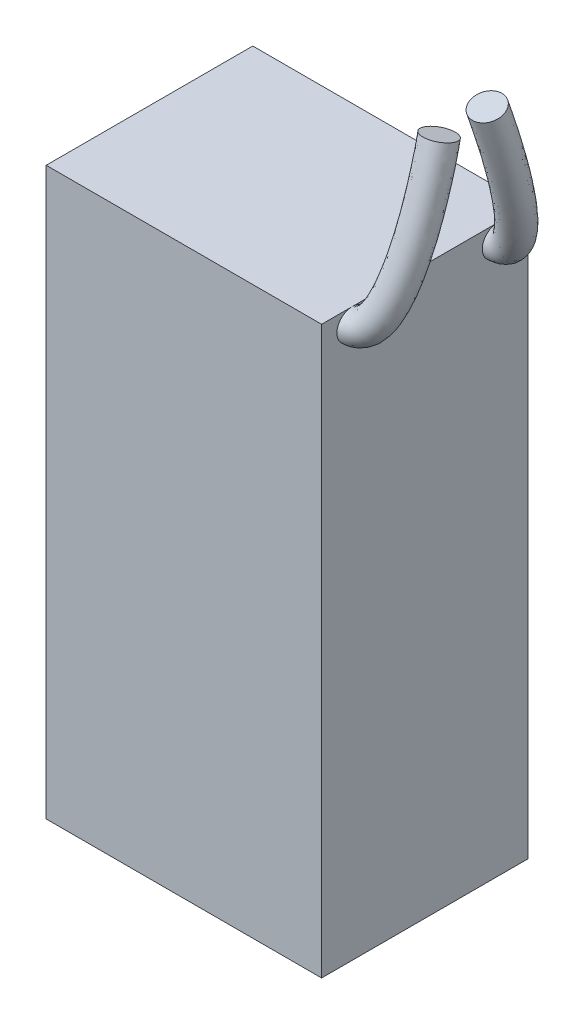
SolidWorks part; units mm, degrees
ref_plane "Спереди" through (0, 0, 0) normal (0, 0, 1) x (1, 0, 0)
ref_plane "Сверху" through (0, 0, 0) normal (0, 1, 0) x (1, 0, 0)
ref_plane "Справа" through (0, 0, 0) normal (1, 0, 0) x (0, 0, -1)
sketch "Эскиз1" plane through (0, 0, 0) normal (0, 1, 0) x (1, 0, 0)
  line L1 (-18, 13.5) -> (18, 13.5)
  line L2 (-18, 13.5) -> (-18, -13.5)
  line L3 (-18, -13.5) -> (18, -13.5)
  line L4 (18, 13.5) -> (18, -13.5)
  line L5 (-18, 13.5) -> (18, -13.5) construction
  line L6 (-18, -13.5) -> (18, 13.5) construction
  point P0 (0, 0)
  dimension "D1" = 36
  dimension "D2" = 27
extrude "Бобышка-Вытянуть1" add sketch "Эскиз1" along normal blind 74
sketch "Эскиз2" plane through (18, 0, 0) normal (1, 0, 0) x (0, 0, -1)
  line L0 (-13.5, 74) -> (13.5, 74) construction
  line L3 (-13.5, 74) -> (-13.5, 0) construction
  circle A0 centre (-9.5, 72) radius 2
  dimension "D1" = 4
  dimension "D2" = 4
sketch "Эскиз7" plane through (18, 0, 0) normal (1, 0, 0) x (0, 0, -1)
  line L0 (13.5, 74) -> (13.5, 0) construction
  line L1 (-13.5, 74) -> (13.5, 74) construction
  circle A0 centre (9.5, 72) radius 2
  dimension "D1" = 4
  dimension "D2" = 4
ref_axis "Ось1" through (18, 72, 9.5) along (-1, 0, 0)
ref_plane "Плоскость1" through (0, 8.8108, 28.8189) normal (0, 0.2924, 0.9563) x (-1, 0, 0)
ref_axis "Ось2" through (18, 72, -9.5) along (-1, 0, 0)
ref_plane "Плоскость2" through (0, 8.8108, -28.8189) normal (0, 0.2924, -0.9563) x (-1, 0, 0)
ref_point "Точка1"
ref_point "Точка2"
sketch "Эскиз4" plane through (0, 8.8108, 28.8189) normal (0, 0.2924, 0.9563) x (-1, 0, 0)
  line L0 (-18, -66.0764) -> (-18, -102.1977) construction
  line L1 (-23, -87.8195) -> (-18, -87.8195) construction
  line L2 (18, -66.8195) -> (-18, -66.8195) construction
  spline S0 degree 3 poles (-18, -66.0764) (-23.7429, -66.2832) (-23.4042, -83.5472) (-23, -87.8195) knots 0 0 0 0 1 1 1 1
  dimension "D1" = 5
  dimension "D2" = 21
sketch "Эскиз6" plane through (0, 8.8108, -28.8189) normal (0, 0.2924, -0.9563) x (-1, 0, 0)
  line L0 (-18, 66.0764) -> (-18, 84.5951) construction
  line L1 (-23, 87.8195) -> (-18, 87.8195) construction
  line L2 (-18, 66.8195) -> (18, 66.8195) construction
  spline S0 degree 3 poles (-18, 66.0764) (-21.8727, 66.2938) (-23.8224, 75.6875) (-23, 87.8195) knots 0 0 0 0 1 1 1 1
  dimension "D1" = 5
  dimension "D2" = 21
sweep "По траектории1" add profiles "Эскиз2" path "Эскиз4"
sweep "По траектории2" add profiles "Эскиз7" path "Эскиз6"
